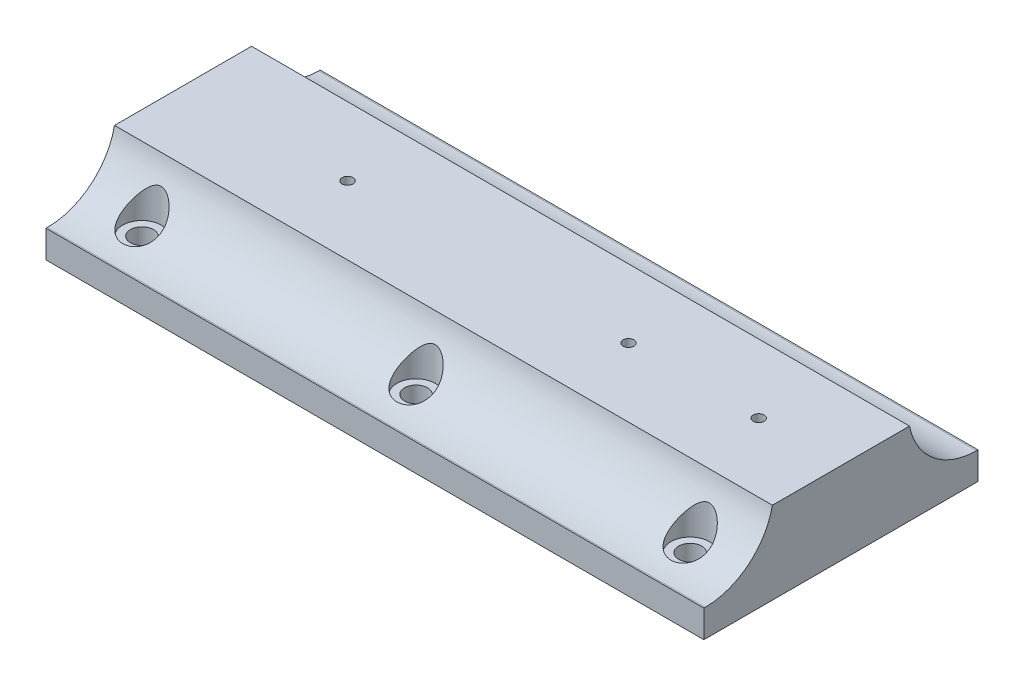
SolidWorks part; units mm, degrees
note: The reader was unsure of these and kept them because the rebuilt part matched: shared geometry of "Skizze7<2>".
ref_plane "Front Plane" through (0, 0, 0) normal (0, 0, 1) x (1, 0, 0)
ref_plane "Top Plane" through (0, 0, 0) normal (0, 1, 0) x (1, 0, 0)
ref_plane "Right Plane" through (0, 0, 0) normal (1, 0, 0) x (0, 0, -1)
sketch "Sketch2" plane through (0, 0, 0) normal (0, 1, 0) x (1, 0, 0)
  line L0 (-46.8981, 34.5466) -> (-46.8981, -15.4534)
  line L1 (-46.8981, -15.4534) -> (73.1019, -15.4534)
  line L2 (73.1019, -15.4534) -> (73.1019, 34.5466)
  line L3 (73.1019, 34.5466) -> (-46.8981, 34.5466)
  dimension "D1" = 120
  dimension "D2" = 50
extrude "Boss-Extrude1" add sketch "Sketch2" along normal blind 15
sketch "Sketch3" plane through (0, 0, 0) normal (0, 1, 0) x (1, 0, 0)
  line L0 (74.3548, 9.5466) -> (-56.2815, 9.5466) construction
  line L1 (63.1019, 9.5466) -> (63.1019, 17.0466)
  line L2 (63.1019, 17.0466) -> (3.1019, 17.0466)
  line L3 (3.1019, 17.0466) -> (3.1019, 19.5466)
  line L4 (3.1019, 19.5466) -> (-36.8981, 19.5466)
  line L5 (-36.8981, 19.5466) -> (-36.8981, 9.5466)
  line L6 (-36.8981, 9.5466) -> (63.1019, 9.5466)
  line L7 (73.1019, -15.4534) -> (73.1019, 34.5466) construction
  line L9 (-46.8981, -15.4534) -> (73.1019, -15.4534) construction
  dimension "D1" = 60
  dimension "D2" = 40
  dimension "D3" = 10
  dimension "D4" = 25
  dimension "D5" = 10
  dimension "D6" = 7.5
revolve "Cut-Revolve8" cut sketch "Sketch3" angle 360 about L0
ref_plane "Ebene1" through (63.1019, 0, 0) normal (-1, 0, 0) x (0, 0, 1)
sketch "Skizze2" plane through (63.1019, 0, 0) normal (-1, 0, 0) x (0, 0, 1)
  line L0 (-22.101, 0) -> (5.7524, 0) construction
  line L1 (-2.0466, 0) -> (-17.0466, 0) construction
  line L2 (-9.5466, -15.2765) -> (-9.5466, 13.7911) construction
  line L3 (-4.5466, 0) -> (-2.0466, 0)
  line L5 (-34.5466, 15) -> (-34.5466, 0) construction
  line L6 (15.4534, 15) -> (15.4534, 0) construction
  line L7 (-6.3324, 3.83) -> (-4.7313, 5.75)
  arc A0 (-2.0466, 0) -> (-4.7313, 5.75) centre (-9.5466, 0) ccw
  arc A1 (-4.5466, 0) -> (-6.3324, 3.83) centre (-9.5466, 0) ccw
  dimension "D1" = 5.75
  dimension "D2" = 7.5
  dimension "D3" = 2.5
  dimension "D4" = 3.83
ref_plane "Ebene2" through (28.1019, 0, 0) normal (-1, 0, 0) x (0, 0, 1)
extrude "Aufsatz-Linear austragen3" add sketch "Skizze2" along normal blind 47.5
ref_plane "Ebene3" through (0, 0, -9.5466) normal (0, 0, 1) x (1, 0, 0)
mirror "Spiegeln1" about plane through (0, 0, -9.5466) normal (0, 0, 1) of "Aufsatz-Linear austragen3"
sketch "Skizze7" plane through (63.1019, 0, 0) normal (-1, 0, 0) x (0, 0, 1)
  line L0 (-4.5466, 0) -> (-14.5466, 0) construction
  circle A0 centre (-9.5466, 0) radius 7.5
  arc A1 (-4.7313, 5.75) -> (-14.362, 5.75) centre (-9.5466, 0) ccw construction
extrude "Schnitt-Linear austragen2" cut sketch "Skizze7" against normal blind 12.5 from surface at 35 starting at plane "Ebene2"
extrude "Schnitt-Linear austragen3" cut sketch "Skizze7<2>" along normal blind 10 contours A0
sketch "Skizze7<2>" plane through (63.1019, 0, 0) normal (-1, 0, 0) x (0, 0, 1) same geometry as "Skizze7"
sketch "Skizze8" plane through (0, 15, 0) normal (0, 1, 0) x (1, 0, 0)
  line L0 (91.3144, 9.5466) -> (-68.5218, 9.5466) construction
  line L1 (73.1019, 34.5466) -> (-46.8981, 34.5466) construction
  line L2 (-46.8981, -15.4534) -> (73.1019, -15.4534) construction
  line L3 (73.1019, -15.4534) -> (73.1019, 34.5466) construction
  line L4 (-46.8981, 34.5466) -> (-46.8981, -15.4534) construction
  circle A0 centre (58.1019, 9.5466) radius 1
  circle A1 centre (34.3519, 9.5466) radius 1
  circle A2 centre (-16.8981, 9.5466) radius 1
  dimension "D1" = 2
  dimension "D2" = 23.75
  dimension "D3" = 15
  dimension "D4" = 30
extrude "Schnitt-Linear austragen4" cut sketch "Skizze8" against normal up to next
sketch "Skizze9" plane through (-46.8981, 0, 0) normal (-1, 0, 0) x (0, 0, 1)
  line L0 (-34.5466, 5) -> (-22.0466, 5)
  line L1 (2.9534, 5) -> (2.9534, 15)
  line L2 (15.4534, 0) -> (-34.5466, 0) construction
  line L4 (2.9534, 5) -> (15.4534, 5)
  line L5 (15.4534, 15) -> (15.4534, 0) construction
  line L6 (-34.5466, 5) -> (-34.5466, 15)
  line L7 (-34.5466, 15) -> (15.4534, 15)
  line L8 (15.4534, 15) -> (15.4534, 5)
  line L9 (2.9534, 15) -> (-22.0466, 15)
  line L10 (-22.0466, 15) -> (-22.0466, 5)
  dimension "D1" = 5
  dimension "D2" = 12.5
  dimension "D3" = 12.5
extrude "Schnitt-Linear austragen5" cut sketch "Skizze9" against normal through all
sketch "Skizze10" plane through (0, 5, 0) normal (0, 1, 0) x (1, 0, 0)
  line L0 (73.1019, 34.5466) -> (73.1019, 22.0466) construction
  line L1 (73.1019, 34.5466) -> (-46.8981, 34.5466) construction
  circle A0 centre (63.1019, 27.0466) radius 2.1
  dimension "D1" = 4.2
  dimension "D2" = 10
  dimension "D3" = 7.5
extrude "Schnitt-Linear austragen7" cut sketch "Skizze10" against normal through all
sketch "Skizze11" plane through (0, 5, 0) normal (0, 1, 0) x (1, 0, 0)
  line L0 (80.5883, 9.5466) -> (-93.0916, 9.5466) construction
  line L1 (73.1019, 34.5466) -> (-46.8981, 34.5466) construction
  line L2 (73.1019, -15.4534) -> (-46.8981, -15.4534) construction
mirror "Spiegeln2" about plane through (0, 0, -9.5466) normal (0, 0, 1) of "Schnitt-Linear austragen7"
ref_plane "Ebene4" through (13.1019, 0, 0) normal (1, 0, 0) x (0, 0, -1)
mirror "Spiegeln3" about plane through (13.1019, 0, 0) normal (1, 0, 0) of "Schnitt-Linear austragen7", "Spiegeln2"
sketch "Skizze12" plane through (0, 5, 0) normal (0, 1, 0) x (1, 0, 0)
  line L0 (73.1019, -15.4534) -> (73.1019, 34.5466) construction
  line L1 (73.1019, 34.5466) -> (-46.8981, 34.5466) construction
  line L2 (73.1019, -15.4534) -> (-46.8981, -15.4534) construction
  circle A0 centre (13.1019, 27.0466) radius 2.1
  circle A1 centre (13.1019, -7.9534) radius 2.1
  circle A2 centre (63.1019, -7.9534) radius 2.1 construction
  dimension "D1" = 60
  dimension "D2" = 7.5
  dimension "D3" = 7.5
extrude "Schnitt-Linear austragen8" cut sketch "Skizze12" against normal blind 10
fillet "Fillet1" radius 12.5 1 edges at (13.1019, 5, 2.9534)
fillet "Fillet2" radius 12.5 1 edges at (13.1019, 5, -22.0466)
ref_plane "Plane1" through (0, 25, 0) normal (0, 1, 0) x (1, 0, 0)
sketch "Sketch4" plane through (0, 25, 0) normal (0, 1, 0) x (1, 0, 0)
  circle A0 centre (63.1019, 27.0466) radius 3.5
  circle A1 centre (13.1019, 27.0466) radius 3.5
  circle A2 centre (-36.8981, 27.0466) radius 3.5
  circle A3 centre (-36.8981, -7.9534) radius 3.5
  circle A4 centre (13.1019, -7.9534) radius 3.5
  circle A5 centre (63.1019, -7.9534) radius 3.5
  dimension "D1" = 7
  dimension "D2" = 7
  dimension "D3" = 7
  dimension "D4" = 7
  dimension "D5" = 7
  dimension "D6" = 7
extrude "Cut-Extrude1" cut sketch "Sketch4" against normal blind 20
